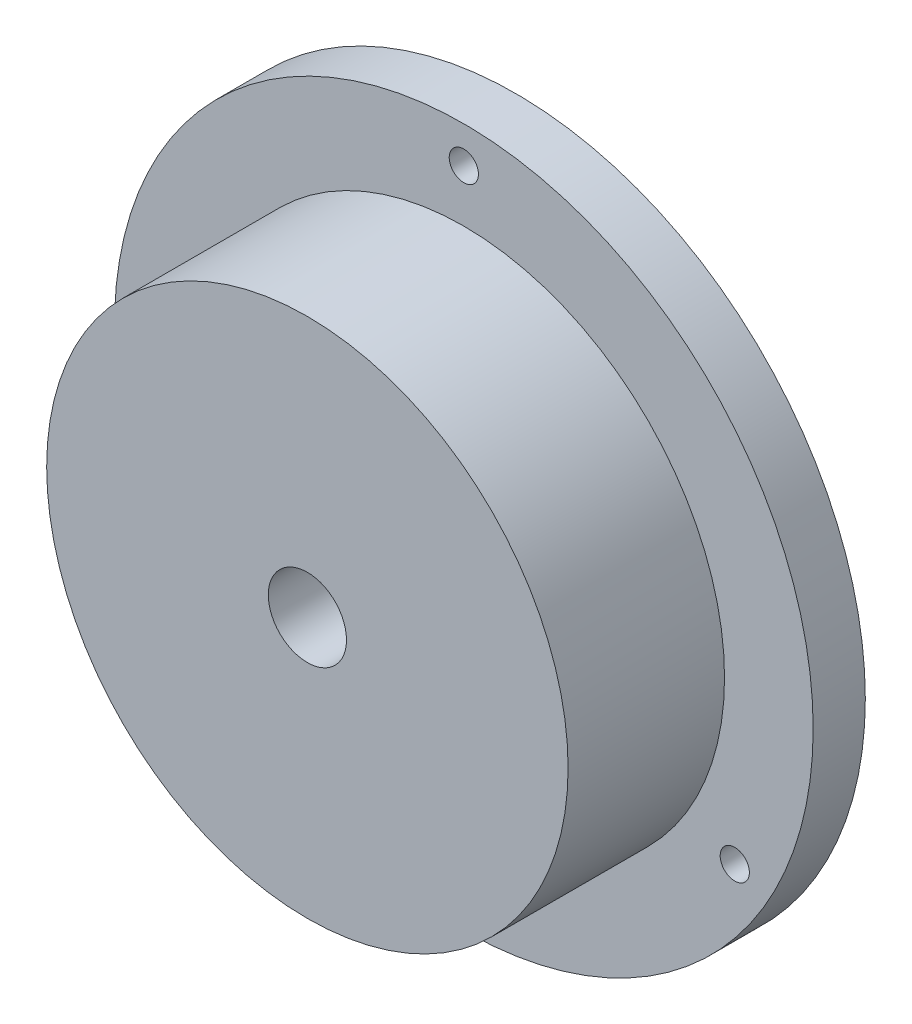
SolidWorks part; units mm, degrees
ref_plane "Front Plane" through (0, 0, 0) normal (0, 0, 1) x (1, 0, 0)
ref_plane "Top Plane" through (0, 0, 0) normal (0, 1, 0) x (1, 0, 0)
ref_plane "Right Plane" through (0, 0, 0) normal (1, 0, 0) x (0, 0, -1)
sketch "Sketch1" plane through (0, 0, 0) normal (0, 0, 1) x (1, 0, 0)
  circle A0 centre (0, 0) radius 21.2725
  dimension "D1" = 42.545
extrude "Boss-Extrude1" add sketch "Sketch1" along normal blind 3.175
sketch "Sketch2" plane through (0, 0, 3.175) normal (0, 0, 1) x (1, 0, 0)
  circle A0 centre (0, 0) radius 15.875
  dimension "D1" = 31.75
extrude "Boss-Extrude2" add sketch "Sketch2" along normal blind 9.525
hole_wizard "3/16 (0.1875) Diameter Hole1" positions "Sketch4" profile "Sketch3" hole size "3/16" standard "Ansi Inch" end condition through all
sketch "Sketch4" plane through (0, 0, 12.7) normal (0, 0, 1) x (1, 0, 0)
  point P1 (0, 0)
sketch "Sketch3" plane through (0, 0, 12.7) normal (1, 0, 0) x (0, -1, 0)
  line L0 (0, 0) -> (0, 12.7)
  line L1 (0, 12.7) -> (2.3812, 12.7)
  line L2 (2.3812, 12.7) -> (2.3812, 0)
  line L5 (2.3812, 0) -> (0, 0)
  line L11 (0, -6.35) -> (0, 107.95) construction
  dimension "Thru Hole Dia." = 4.7625
  dimension "Thru Hole Depth" = 12.7
hole_wizard "#2-56 Tapped Hole3" positions "Sketch10" profile "Sketch9" tap size "#2-56" standard "Ansi Inch" end condition through all
sketch "Sketch10" plane through (0, 0, 3.175) normal (0, 0, 1) x (1, 0, 0)
  point P1 (0, 19.05)
  dimension "D1" = 19.05
sketch "Sketch9" plane through (0, 19.05, 3.175) normal (1, 0, 0) x (0, -1, 0)
  line L0 (0, 0) -> (0, 3.175)
  line L1 (0, 3.175) -> (0.889, 3.175)
  line L2 (0.889, 3.175) -> (0.889, 0)
  line L5 (0.889, 0) -> (0, 0)
  line L11 (0, -6.35) -> (0, 107.95) construction
  dimension "Thread Major Dia." = 1.778
  dimension "Thru Tap Drill Depth" = 3.175
pattern_circular "CirPattern1" count 3 every 120 about axis through (0, 0, 3.175) along (0, 0, 1) of "#2-56 Tapped Hole3"
sketch "Sketch11" plane through (0, 0, 0) normal (0, 0, -1) x (-1, 0, 0)
  line L0 (0, 0) -> (0, -21.2725) construction
  circle A1 centre (0, 0) radius 21.2725 construction
ref_plane "Plane1" through (0, -21.2725, 0) normal (0, -1, 0) x (1, 0, 0)
hole_wizard "#8-32 Tapped Hole1" positions "Sketch13" profile "Sketch12" tap size "#8-32" standard "Ansi Inch"
sketch "Sketch13" plane through (0, -21.2725, 0) normal (0, -1, 0) x (1, 0, 0)
  line L0 (-21.2725, 0) -> (21.2725, 0) construction
  point P1 (0, 7.9248)
  dimension "D1" = 7.9248
sketch "Sketch12" plane through (0, -21.2725, 7.9248) normal (1, 0, 0) x (0, 0, -1)
  line L0 (0, 0) -> (0, 22.3093)
  line L1 (0, 22.3093) -> (1.7272, 21.2715)
  line L2 (1.7272, 21.2715) -> (1.7272, 0)
  line L5 (1.7272, 0) -> (0, 0)
  line L10 (0, 22.3093) -> (-1.7272, 21.2715) construction
  line L11 (0, -6.35) -> (0, 107.95) construction
  dimension "Tap Drill Dia." = 3.4544
  dimension "Tap Drill Depth" = 21.2715
  dimension "Drill Angle" = 118
sketch "Sketch14" plane through (0, 0, 0) normal (0, 0, -1) x (-1, 0, 0)
  circle A0 centre (0, 0) radius 7.9375
  dimension "D1" = 15.875
extrude "Cut-Extrude1" cut sketch "Sketch14" against normal blind 3.8862
